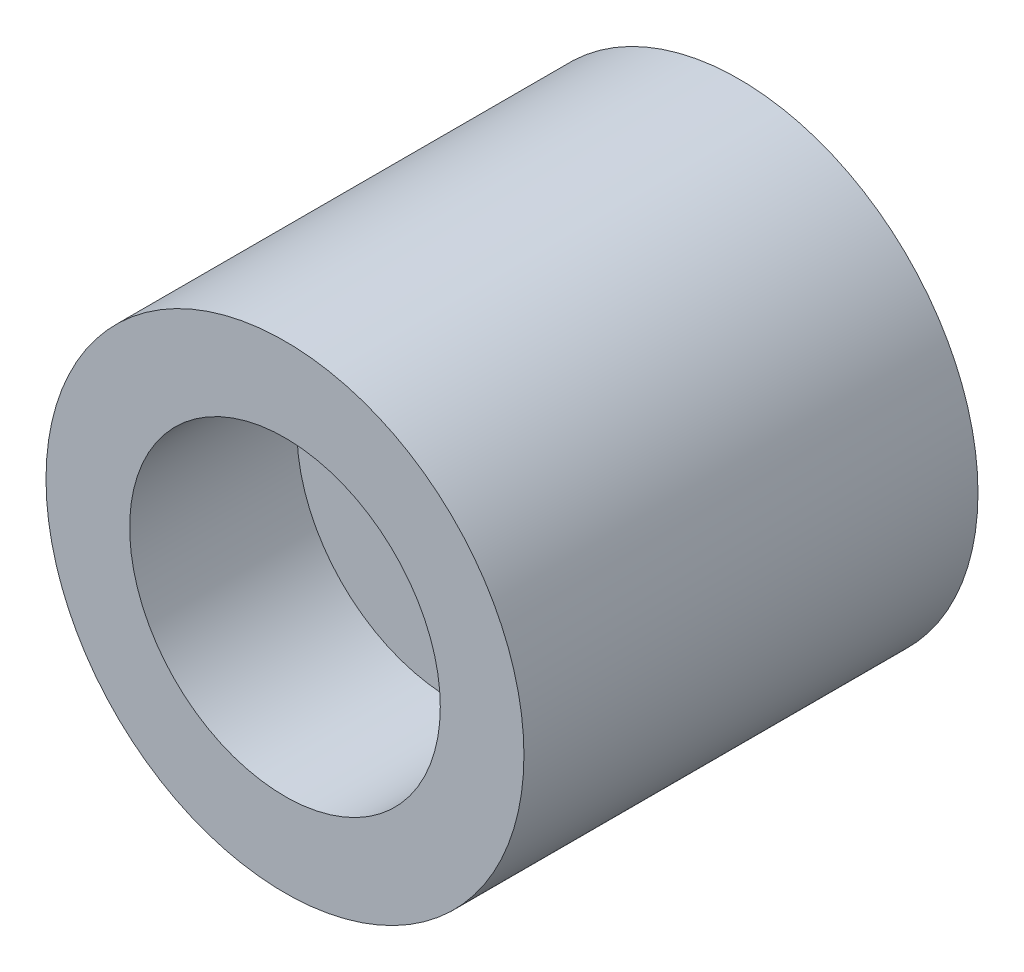
SolidWorks part; units mm, degrees
material "3.1355 (EN-AW 2024)"
ref_plane "Front" through (0, 0, 0) normal (0, 0, 1) x (1, 0, 0)
ref_plane "Top" through (0, 0, 0) normal (0, 1, 0) x (1, 0, 0)
ref_plane "Right" through (0, 0, 0) normal (1, 0, 0) x (0, 0, -1)
sketch "Эскиз1" plane through (0, 0, 0) normal (0, 0, 1) x (1, 0, 0)
  circle A0 centre (0, 0) radius 10
  dimension "D1" = 20
extrude "Бобышка-Вытянуть1" add sketch "Эскиз1" along normal blind 19
sketch "Эскиз2" plane through (0, 0, 19) normal (0, 0, 1) x (1, 0, 0)
  circle A0 centre (0, 0) radius 6.5
  dimension "D1" = 13
extrude "Вырез-Вытянуть1" cut sketch "Эскиз2" against normal blind 7
